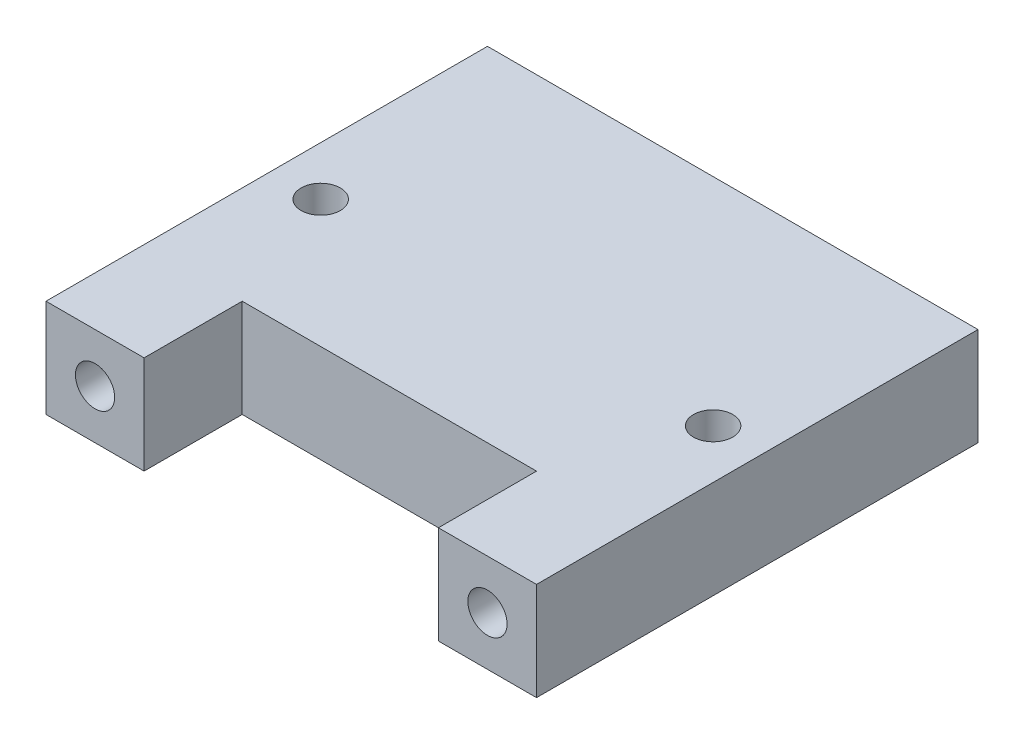
SolidWorks part; units mm, degrees
material "PVC rigide"
ref_plane "Plan de face" through (0, 0, 0) normal (0, 0, 1) x (1, 0, 0)
ref_plane "Plan de dessus" through (0, 0, 0) normal (0, 1, 0) x (1, 0, 0)
ref_plane "Plan de droite" through (0, 0, 0) normal (1, 0, 0) x (0, 0, -1)
sketch "Esquisse1" plane through (0, 0, 0) normal (0, 1, 0) x (1, 0, 0)
  line L0 (-47.1481, 1.0417) -> (-47.1481, 11.0417)
  line L1 (-57.1481, 46.0417) -> (-7.1481, 46.0417)
  line L2 (-57.1481, 46.0417) -> (-57.1481, 1.0417)
  line L3 (-57.1481, 1.0417) -> (-47.1481, 1.0417)
  line L4 (-7.1481, 46.0417) -> (-7.1481, 16.0417)
  line L5 (-47.1481, 11.0417) -> (-17.1481, 11.0417)
  line L6 (-17.1481, 11.0417) -> (-17.1481, 1.0417)
  line L7 (-17.1481, 1.0417) -> (-7.1481, 1.0417)
  line L8 (-7.1481, 1.0417) -> (-7.1481, 16.0417)
  dimension "D1" = 50
  dimension "D2" = 45
  dimension "D3" = 10
  dimension "D5" = 10
extrude "Boss.-Extru.1" add sketch "Esquisse1" along normal blind 10
sketch "Esquisse2" plane through (0, 0, -1.0417) normal (0, 0, 1) x (1, 0, 0)
  line L0 (-57.1481, 10) -> (-47.1481, 0) construction
  line L1 (-57.1481, 0) -> (-47.1481, 10) construction
  line L2 (-17.1481, 10) -> (-7.1481, 0) construction
  line L3 (-17.1481, 0) -> (-7.1481, 10) construction
  line L4 (-47.1481, 10) -> (-17.1481, 10) construction
  line L5 (-17.1481, 10) -> (-17.1481, 0) construction
  circle A0 centre (-52.1481, 5) radius 2
  circle A1 centre (-12.1481, 5) radius 2
  point P8 (-52.1481, 5)
  point P15 (-12.1481, 5)
  dimension "D1" = 4
extrude "Enlèv. mat.-Extru.1" cut sketch "Esquisse2" against normal blind 10
sketch "Esquisse3" plane through (0, 0, -46.0417) normal (0, 0, -1) x (-1, 0, 0)
  line L0 (7.1481, 5) -> (57.1481, 5) construction
  line L1 (7.1481, 10) -> (7.1481, 0) construction
  line L2 (57.1481, 10) -> (57.1481, 0) construction
  circle A0 centre (12.1481, 5) radius 2
  circle A1 centre (52.1481, 5) radius 2
  dimension "D1" = 4
  dimension "D2" = 5
  dimension "D3" = 5
extrude "Enlèv. mat.-Extru.2" cut sketch "Esquisse3" against normal blind 10
sketch "Esquisse4" plane through (0, 10, 0) normal (0, 1, 0) x (1, 0, 0)
  line L0 (-62.8741, 24.0417) -> (2.0024, 24.0417) construction
  line L1 (-7.1481, 46.0417) -> (-57.1481, 46.0417) construction
  line L2 (-57.1481, 46.0417) -> (-57.1481, 1.0417) construction
  line L3 (-7.1481, 1.0417) -> (-7.1481, 46.0417) construction
  circle A0 centre (-52.1481, 24.0417) radius 2
  circle A1 centre (-12.1481, 24.0417) radius 2
  dimension "D2" = 4
  dimension "D1" = 22
  dimension "D3" = 5
  dimension "D4" = 5
extrude "Enlèv. mat.-Extru.3" cut sketch "Esquisse4" against normal blind 10
chamfer "Chanfrein1" distance 2.5 angle 45 2 edges at (-52.1481, 0, -22.0417) (-12.1481, 0, -22.0417)
